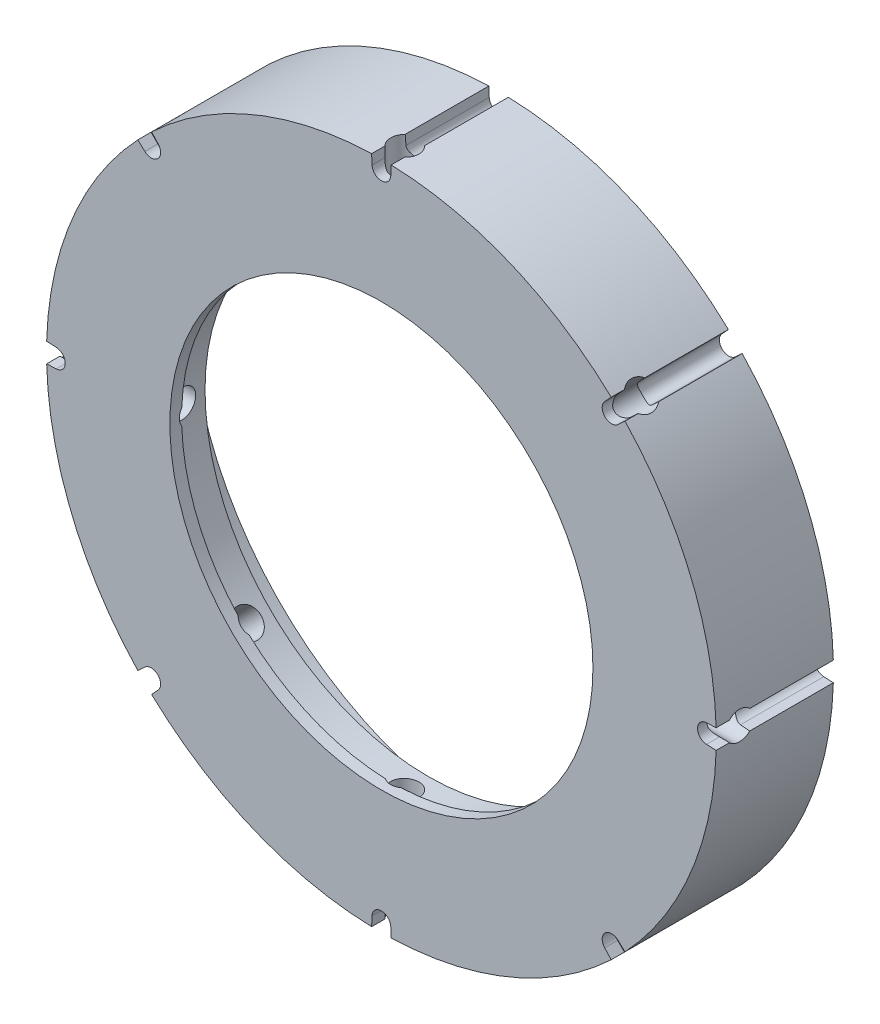
SolidWorks part; units mm, degrees
ref_plane "Front Plane" through (0, 0, 0) normal (0, 0, 1) x (1, 0, 0)
ref_plane "Top Plane" through (0, 0, 0) normal (0, 1, 0) x (1, 0, 0)
ref_plane "Right Plane" through (0, 0, 0) normal (1, 0, 0) x (0, 0, -1)
sketch "Sketch1" plane through (0, 0, 0) normal (0, 0, 1) x (1, 0, 0)
  circle A4 centre (0, 0) radius 14.2875
  circle A5 centre (0, 0) radius 13.15
  circle A6 centre (0, 0) radius 13.15
  dimension "D1" = 0.15
  dimension "D3" = 1.1375
  dimension "D2" = 28.575
extrude "Boss-Extrude1" add sketch "Sketch1" against normal blind 3
sketch "Sketch2" plane through (0, 0, 0) normal (0, 0, 1) x (1, 0, 0)
  circle A0 centre (0, 0) radius 14.2875
  circle A1 centre (0, 0) radius 9.025
  circle A2 centre (0, 0) radius 14.2875 construction
  dimension "D1" = 18.05
extrude "Boss-Extrude2" add sketch "Sketch2" along normal blind 2
sketch "Sketch3" plane through (0, 0, 2) normal (0, 0, 1) x (1, 0, 0)
  circle A0 centre (0, 0) radius 13.15 construction
  circle A1 centre (0, 0) radius 14.2875
  circle A2 centre (0, 0) radius 14.2875
  circle A3 centre (0, 0) radius 13.15
  dimension "D1" = 0
sketch "Sketch4" plane through (0, 0, 0) normal (0, 0, -1) x (-1, 0, 0)
  circle A1 centre (0, 0) radius 9.525
extrude "Cut-Extrude2" cut sketch "Sketch4" against normal blind 1.5
sketch "Sketch5" plane through (0, 0, -3) normal (0, 0, -1) x (-1, 0, 0)
  line L0 (-13.8709, 0.3997) -> (-14.2814, 0.4167)
  line L1 (-13.8709, -0.3997) -> (-14.2814, -0.4167)
  circle A3 centre (0, 0) radius 14.2875 construction
  circle A5 centre (0, 0) radius 14.2875
  circle A6 centre (-13.8875, 0) radius 0.4
  circle M4 centre (0, 0) radius 14.2875
extrude "Cut-Extrude4" cut sketch "Sketch5" against normal through all contours A6 | A6 L0 M4 | A6 A5 L1 region at (14.1918, 0.3195, -3) region at (13.8875, 0, -3) region at (14.1918, -0.3195, -3)
ref_plane "Plane1" through (14.2814, 0, 0) normal (1, 0, 0) x (0, 0, -1)
sketch "Sketch6" plane through (14.2814, 0, 0) normal (1, 0, 0) x (0, 0, -1)
  line L0 (-2, 0.4167) -> (3, 0.4167) construction
  line L1 (-2, 0.4167) -> (3, 0.4167)
  circle A0 centre (-1, 0) radius 0.6
extrude "Cut-Extrude5" cut sketch "Sketch6" against normal blind 10 contours L1 A0 | L1 A0 region at (14.2814, 0.4911, 1) region at (14.2814, -0.0525, 1)
sketch "Sketch7" plane through (0, 0, 0) normal (0, 1, 0) x (1, 0, 0)
  line L0 (0, 0) -> (0, 6.608) construction
pattern_circular "CirPattern1" count 8 over 360 about axis through (0, 0, 0) along (0, 0, -1) of "Cut-Extrude5", "Cut-Extrude4"
